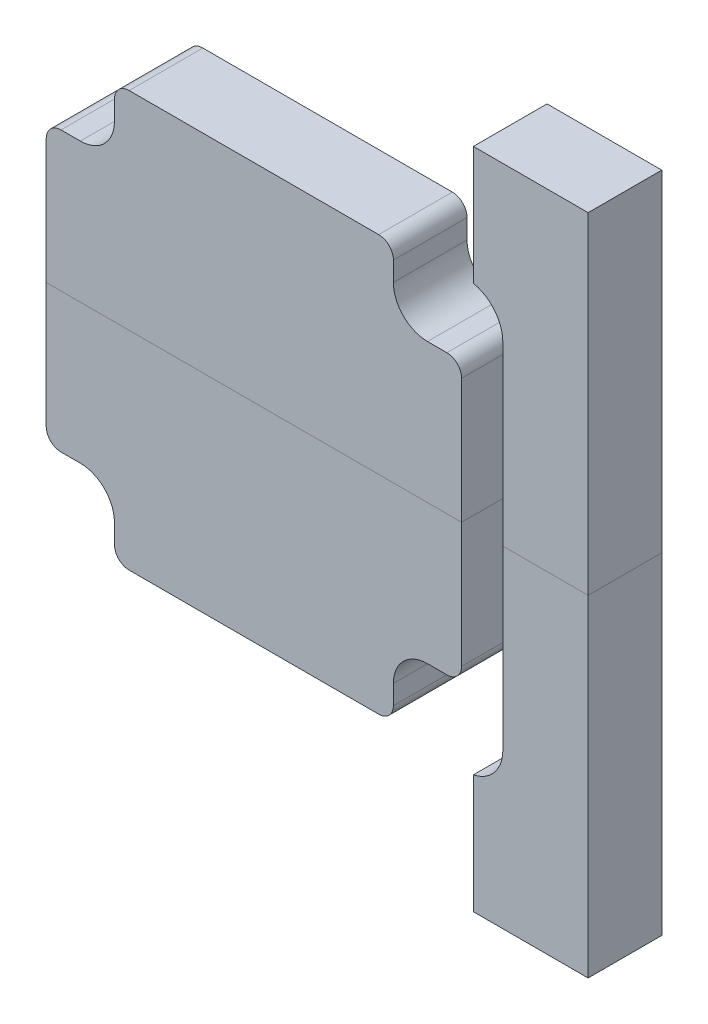
SolidWorks part; units mm, degrees
ref_plane "Front Plane" through (0, 0, 0) normal (0, 0, 1) x (1, 0, 0)
ref_plane "Top Plane" through (0, 0, 0) normal (0, 1, 0) x (1, 0, 0)
ref_plane "Right Plane" through (0, 0, 0) normal (1, 0, 0) x (0, 0, -1)
ref_axis "Axis1" through (0, -55, 0) along (0, 1, 0)
sketch "Sketch1" plane through (0, 0, 0) normal (0, 0, 1) x (1, 0, 0)
  line L4 (-162.76, -16.94) -> (-162.76, 16.94) construction
  line L5 (-164.76, 18.94) -> (-167.39, 18.94) construction
  line L6 (-172.02, 23.57) -> (-172.02, 26.2) construction
  line L7 (-174.02, 28.2) -> (-207.9, 28.2) construction
  line L8 (-209.9, 26.2) -> (-209.9, 23.57) construction
  line L9 (-214.53, 18.94) -> (-217.16, 18.94) construction
  line L10 (-219.16, 16.94) -> (-219.16, -16.94) construction
  line L16 (-162.76, 0) -> (-162.76, 16.94)
  line L17 (-164.76, 18.94) -> (-167.39, 18.94)
  line L18 (-172.02, 23.57) -> (-172.02, 26.2)
  line L19 (-174.02, 28.2) -> (-207.9, 28.2)
  line L20 (-209.9, 26.2) -> (-209.9, 23.57)
  line L21 (-214.53, 18.94) -> (-217.16, 18.94)
  line L22 (-219.16, 16.94) -> (-219.16, 0)
  line L25 (-145.58, 45) -> (-145.58, -45) construction
  line L26 (-145.58, 45) -> (-145.58, 0)
  line L27 (-151.16, 45) -> (-145.58, 45) construction
  line L28 (-151.16, 45) -> (-145.58, 45)
  line L29 (-161.16, 45) -> (-151.16, 45) construction
  line L30 (-161.16, 45) -> (-151.16, 45)
  line L31 (-161.16, 32.5) -> (-161.16, 40) construction
  line L32 (-161.16, 28.899) -> (-161.16, 45)
  line L33 (-157.16, -29.5) -> (-157.16, 29.5) construction
  line L34 (-157.16, 0) -> (-157.16, 24)
  line L35 (-219.16, 0) -> (-145.58, 0) construction
  line L36 (-219.16, 0) -> (-162.76, 0)
  line L37 (-145.58, 0) -> (-157.16, 0)
  arc A4 (-162.76, 16.94) -> (-164.76, 18.94) centre (-164.76, 16.94) ccw construction
  arc A5 (-172.02, 23.57) -> (-167.39, 18.94) centre (-167.39, 23.57) ccw construction
  arc A6 (-172.02, 26.2) -> (-174.02, 28.2) centre (-174.02, 26.2) ccw construction
  arc A7 (-207.9, 28.2) -> (-209.9, 26.2) centre (-207.9, 26.2) ccw construction
  arc A8 (-214.53, 18.94) -> (-209.9, 23.57) centre (-214.53, 23.57) ccw construction
  arc A9 (-217.16, 18.94) -> (-219.16, 16.94) centre (-217.16, 16.94) ccw construction
  arc A16 (-162.76, 16.94) -> (-164.76, 18.94) centre (-164.76, 16.94) ccw
  arc A17 (-172.02, 23.57) -> (-167.39, 18.94) centre (-167.39, 23.57) ccw
  arc A18 (-172.02, 26.2) -> (-174.02, 28.2) centre (-174.02, 26.2) ccw
  arc A19 (-207.9, 28.2) -> (-209.9, 26.2) centre (-207.9, 26.2) ccw
  arc A20 (-214.53, 18.94) -> (-209.9, 23.57) centre (-214.53, 23.57) ccw
  arc A21 (-217.16, 18.94) -> (-219.16, 16.94) centre (-217.16, 16.94) ccw
  arc A24 (-157.16, 24) -> (-162.16, 29) centre (-162.16, 24) ccw construction
  arc A25 (-157.16, 24) -> (-161.16, 28.899) centre (-162.16, 24) ccw
extrude "Boss-Extrude1" add sketch "Sketch1" along normal blind 10
mirror "Mirror1" about plane through (-219.16, 0, 10) normal (0, 1, 0) of bodies 102 101
